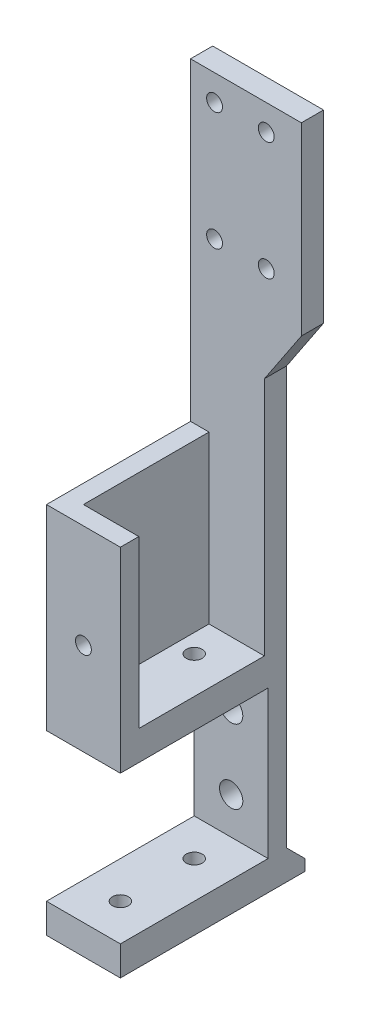
SolidWorks part; units mm, degrees
ref_plane "前视基准面" through (0, 0, 0) normal (0, 0, 1) x (1, 0, 0)
ref_plane "上视基准面" through (0, 0, 0) normal (0, 1, 0) x (1, 0, 0)
ref_plane "右视基准面" through (0, 0, 0) normal (1, 0, 0) x (0, 0, -1)
sketch "草图1" plane through (0, 0, 0) normal (0, 1, 0) x (1, 0, 0)
  line L1 (0, 0) -> (35, 0)
  line L2 (0, 0) -> (0, 80)
  line L3 (0, 80) -> (35, 80)
  line L4 (35, 0) -> (35, 80)
  circle A0 centre (25, 30) radius 2.15
  circle A1 centre (25, 10) radius 2.15
  dimension "D6" = 4.3
  dimension "D1" = 35
  dimension "D2" = 80
  dimension "D3" = 10
  dimension "D4" = 10
  dimension "D5" = 20
extrude "凸台-拉伸1" add sketch "草图1" along normal blind 30
sketch "草图3" plane through (0, 30, 0) normal (0, 1, 0) x (1, 0, 0)
  line L0 (35, 0) -> (35, 80) construction
  line L1 (35, 40) -> (0, 40)
  line L2 (35, 40) -> (35, 45)
  line L3 (35, 45) -> (0, 45)
  line L4 (0, 40) -> (0, 45)
  line L5 (0, 80) -> (0, 0) construction
  line L6 (0, 0) -> (35, 0) construction
  dimension "D1" = 5
  dimension "D2" = 40
extrude "凸台-拉伸2" add sketch "草图3" along normal blind 40
sketch "草图4" plane through (0, 0, 0) normal (-1, 0, 0) x (0, 0, 1)
  line L0 (-40, 70) -> (-40, 30) construction
  line L1 (0, 0) -> (-40, 0)
  line L2 (0, 0) -> (0, 22)
  line L3 (0, 22) -> (-40, 22)
  line L4 (-40, 0) -> (-40, 22)
  line L5 (-80, 30) -> (-50, 30)
  line L6 (-80, 30) -> (-80, 10)
  line L7 (-80, 10) -> (-50, 10)
  line L8 (-50, 30) -> (-50, 10)
  line L10 (-40, 30) -> (0, 30) construction
  line L11 (-45, 70) -> (-45, 30) construction
  dimension "D1" = 8
  dimension "D2" = 20
  dimension "D3" = 5
extrude "切除-拉伸2" cut sketch "草图4" against normal blind 70
chamfer "倒角1" distance 5 angle 45 1 edges at (17.5, 30, -50)
sketch "草图7" plane through (0, 0, -45) normal (0, 0, -1) x (-1, 0, 0)
  line L0 (-35, 70) -> (-35, 30) construction
  line L1 (-35, 70) -> (0, 70) construction
  circle A0 centre (-25, 60) radius 3.15
  circle A1 centre (-25, 40) radius 3.15
  dimension "D2" = 6.3
  dimension "D1" = 10
  dimension "D3" = 10
  dimension "D4" = 20
extrude "切除-拉伸3" cut sketch "草图7" against normal blind 70
sketch "草图8" plane through (0, 30, 0) normal (0, 1, 0) x (1, 0, 0)
  line L0 (0, 0) -> (15, 0)
  line L1 (0, 0) -> (35, 0) construction
  line L2 (15, 0) -> (0, 36)
  line L3 (0, 40) -> (0, 0) construction
  line L4 (0, 36) -> (0, 0)
  dimension "D1" = 20
  dimension "D2" = 4
extrude "切除-拉伸4" cut sketch "草图8" against normal blind 70
sketch "草图9" plane through (0, 70, 0) normal (0, 1, 0) x (1, 0, 0)
  line L0 (35, 45) -> (0, 45) construction
  line L1 (35, 45) -> (0, 45)
  line L5 (0, 40) -> (0, 36)
  line L6 (0, 36) -> (15, 0)
  line L7 (15, 0) -> (35, 0)
  line L8 (35, 0) -> (35, 40)
  line L9 (35, 40) -> (0, 40)
  line L10 (0, 45) -> (0, 36)
  line L11 (0, 36) -> (15, 0)
  line L12 (15, 0) -> (35, 0)
  line L13 (35, 0) -> (35, 45)
  circle A0 centre (25, 30) radius 2.15 construction
  circle A1 centre (25, 30) radius 2.15
  circle A2 centre (25, 10) radius 2.15 construction
  circle A3 centre (25, 10) radius 2.15
  dimension "D1" = 0
extrude "凸台-拉伸3" add sketch "草图9" along normal blind 8
sketch "草图10" plane through (0, 0, 0) normal (-1, 0, 0) x (0, 0, 1)
  line L0 (-45, 78) -> (-40, 78) construction
  line L45 (-45, 78) -> (-45, 30) construction
  line L46 (-40, 70) -> (-40, 30) construction
  line L47 (0, 30) -> (-36, 30) construction
  line L48 (-80, 156) -> (-40, 156)
  line L49 (-80, 146) -> (-80, 156)
  line L50 (-50, 146) -> (-80, 146)
  line L51 (-40, 22) -> (-36, 22)
  line L52 (-36, 22) -> (-36, 30)
  line L53 (-36, 30) -> (-40, 30)
  line L54 (-40, 30) -> (-40, 70)
  line L55 (-40, 70) -> (-36, 70)
  line L56 (-36, 70) -> (-36, 78)
  line L57 (-36, 78) -> (-45, 78)
  line L58 (-45, 78) -> (-45, 30)
  line L59 (-45, 30) -> (-50, 25)
  line L60 (-50, 25) -> (-50, 10)
  line L61 (-50, 10) -> (-80, 10)
  line L62 (-80, 10) -> (-80, 0)
  line L63 (-80, 0) -> (-40, 0)
  line L64 (-40, 0) -> (-40, 22)
  line L65 (-40, 22) -> (-36, 22)
  line L66 (-36, 22) -> (-36, 30)
  line L67 (-36, 30) -> (-40, 30)
  line L68 (-40, 30) -> (-40, 78)
  line L72 (-45, 126) -> (-45, 78)
  line L73 (-45, 30) -> (-50, 25)
  line L74 (-50, 25) -> (-50, 10)
  line L75 (-50, 10) -> (-80, 10)
  line L76 (-80, 10) -> (-80, 0)
  line L77 (-80, 0) -> (-40, 0)
  line L78 (-40, 0) -> (-40, 22)
  line L79 (-50, 131) -> (-50, 146)
  line L80 (-45, 126) -> (-50, 131)
  line L81 (-40, 156) -> (-40.5, 78)
  line L82 (-45, 78) -> (-36, 78) construction
  line L83 (-40.5, 78) -> (-45, 78)
  line L84 (-45, 78) -> (-45, 30)
  line M23 (-36, 78) -> (-45, 78)
  line M24 (-45, 78) -> (-45, 30)
  dimension "D2" = 48
  dimension "D1" = 0
extrude "凸台-拉伸4" add sketch "草图10" against normal through all contours L50 M24 M23 region at (0, 155.1234, -60)
sketch "草图2" plane through (0, 30, 0) normal (0, 1, 0) x (1, 0, 0)
  line L0 (0, 40) -> (0, 36) construction
  line L1 (35, 80) -> (0, 80) construction
  circle A0 centre (10, 70) radius 4.1
  dimension "D3" = 8.2
  dimension "D1" = 10
  dimension "D2" = 10
extrude "切除-拉伸5" cut sketch "草图2" against normal through all and the other way through all
sketch "草图11" plane through (0, 0, 0) normal (0, 0, 1) x (1, 0, 0)
  line L0 (35, 0) -> (0, 0) construction
  line L1 (0, 156) -> (15, 156)
  line L2 (0, 156) -> (0, 0)
  line L3 (0, 0) -> (15, 0)
  line L4 (15, 156) -> (15, 0)
  line L5 (35, 22) -> (35, 0) construction
  dimension "D1" = 20
extrude "切除-拉伸6" cut sketch "草图11" against normal through all and the other way through all
sketch "草图13" plane through (35, 0, 0) normal (1, 0, 0) x (0, 0, -1)
  line L1 (40, 22) -> (80, 22)
  line L2 (40, 22) -> (40, 0)
  line L3 (40, 0) -> (80, 0)
  line L4 (80, 22) -> (80, 0)
extrude "切除-拉伸7" cut sketch "草图13" against normal through all
sketch "草图19" plane through (15, 0, 0) normal (-1, 0, 0) x (0, 0, 1)
  line L0 (0, 78) -> (-40.5, 78) construction
  line L1 (-80, 156) -> (-34.0016, 156)
  line L2 (-80, 156) -> (-80, 78)
  line L3 (-80, 78) -> (-34.0016, 78)
  line L4 (-34.0016, 156) -> (-34.0016, 78)
extrude "切除-拉伸11" cut sketch "草图19" against normal blind 56
sketch "草图21" plane through (0, 0, -45) normal (0, 0, -1) x (-1, 0, 0)
  line L0 (-35, 78) -> (-35, 208)
  line L1 (-35, 208) -> (-5, 208)
  line L2 (-5, 208) -> (-5, 158)
  line L3 (-5, 158) -> (-15, 143)
  line L4 (-15, 143) -> (-15, 78)
  line L5 (-35, 78) -> (-15, 78)
  circle A0 centre (-28.5, 201) radius 2.15
  circle A1 centre (-14.5, 201) radius 2.15
  circle A2 centre (-28.5, 169) radius 2.15
  circle A3 centre (-14.5, 169) radius 2.15
  dimension "D9" = 4.3
  dimension "D1" = 30
  dimension "D2" = 50
  dimension "D3" = 15
  dimension "D4" = 130
  dimension "D5" = 6.5
  dimension "D6" = 14
  dimension "D7" = 7
  dimension "D8" = 32
extrude "凸台-拉伸8" add sketch "草图21" against normal blind 6
sketch "草图22" plane through (35, 0, 0) normal (1, 0, 0) x (0, 0, -1)
  line L0 (0, 78) -> (39, 78)
  line L1 (39, 78) -> (39, 123)
  line L2 (39, 208) -> (39, 78) construction
  line L5 (0, 123) -> (0, 78)
  line L6 (39, 123) -> (0, 123)
  dimension "D1" = 45
  dimension "D2" = 45
extrude "凸台-拉伸9" add sketch "草图22" against normal blind 5
sketch "草图23" plane through (0, 0, 0) normal (0, 0, 1) x (1, 0, 0)
  line L1 (35, 70) -> (15, 70)
  line L2 (35, 70) -> (35, 123)
  line L3 (35, 123) -> (15, 123)
  line L4 (15, 70) -> (15, 123)
  circle A0 centre (25, 95) radius 2.15
  dimension "D5" = 4.3
  dimension "D1" = 20
  dimension "D2" = 10
  dimension "D3" = 25
extrude "凸台-拉伸10" add sketch "草图23" against normal blind 5
mirror "镜向1" about plane through (35, 30, 0) normal (-1, 0, 0) of bodies 126
sketch "草图24" plane through (5, 0, 0) normal (-1, 0, 0) x (0, 0, 1)
  line L1 (-108.2992, 243.5529) -> (37.9397, 243.5529)
  line L2 (-108.2992, 243.5529) -> (-108.2992, -7.8216)
  line L3 (-108.2992, -7.8216) -> (37.9397, -7.8216)
  line L4 (37.9397, 243.5529) -> (37.9397, -7.8216)
extrude "切除-拉伸12" cut sketch "草图24" against normal up to vertex (30 mm away) up to point (35, 208, -39)
